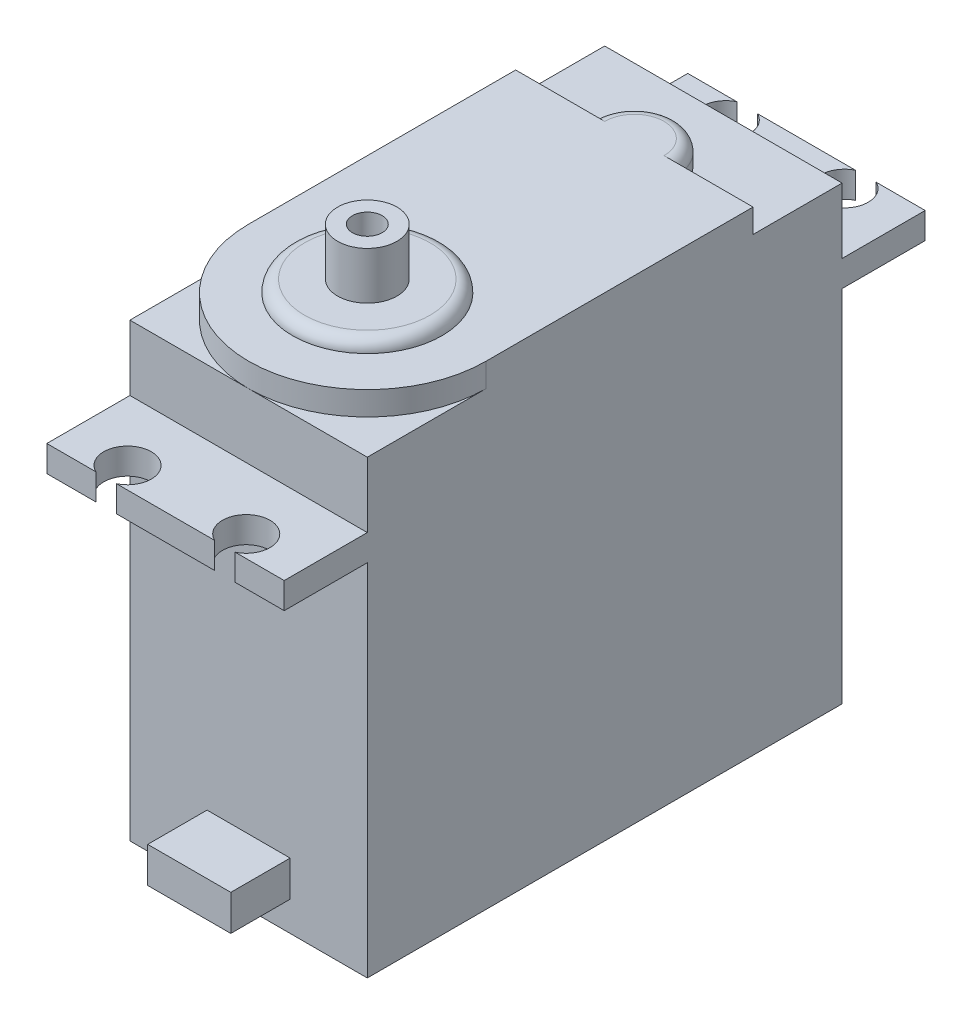
SolidWorks part; units mm, degrees
ref_plane "Front Plane" through (0, 0, 0) normal (0, 0, 1) x (1, 0, 0)
ref_plane "Top Plane" through (0, 0, 0) normal (0, 1, 0) x (1, 0, 0)
ref_plane "Right Plane" through (0, 0, 0) normal (1, 0, 0) x (0, 0, -1)
sketch "Sketch1" plane through (0, 0, 0) normal (0, 1, 0) x (1, 0, 0)
  line L1 (0, 0) -> (20, 0)
  line L2 (0, 0) -> (0, 40)
  line L3 (0, 40) -> (20, 40)
  line L4 (20, 0) -> (20, 40)
  dimension "D1" = 40
  dimension "D2" = 20
extrude "Boss-Extrude1" add sketch "Sketch1" along normal blind 38
sketch "Sketch2" plane through (0, 0, 0) normal (0, 0, 1) x (1, 0, 0)
  line L0 (6.5, 2.5) -> (0, 0) construction
  line L1 (6.5, 2.5) -> (13.5, 2.5)
  line L2 (6.5, 2.5) -> (6.5, 5.5)
  line L3 (6.5, 5.5) -> (13.5, 5.5)
  line L4 (13.5, 2.5) -> (13.5, 5.5)
  line L5 (13.5, 2.5) -> (20, 0) construction
  line L6 (0, 0) -> (20, 0) construction
  dimension "D1" = 7
  dimension "D2" = 3
  dimension "." = 2.5
extrude "Boss-Extrude2" add sketch "Sketch2" along normal blind 5
sketch "Sketch3" plane through (0, 38, 0) normal (0, 1, 0) x (1, 0, 0)
  line L0 (0, 0) -> (20, 0) construction
  line L1 (10, 10) -> (0, 0) construction
  line L2 (10, 10) -> (20, 0) construction
  line L3 (20, 0) -> (20, 40) construction
  circle A0 centre (10, 10) radius 2.5
  dimension "D1" = 10
  dimension "D2" = 5
extrude "Boss-Extrude3" add sketch "Sketch3" along normal blind 7
sketch "Sketch4" plane through (0, 0, 0) normal (0, 0, 1) x (1, 0, 0)
  line L0 (0, 38) -> (0, 0) construction
  line L1 (0, 32.5) -> (20, 32.5)
  line L2 (0, 32.5) -> (0, 30.3)
  line L3 (0, 30.3) -> (20, 30.3)
  line L4 (20, 32.5) -> (20, 30.3)
  line L5 (20, 38) -> (20, 0) construction
  line L6 (0, 38) -> (20, 38) construction
  dimension "D1" = 2.2
  dimension "D2" = 5.5
extrude "Boss-Extrude4" add sketch "Sketch4" along normal blind 7 and the other way blind 47
sketch "Sketch5" plane through (0, 32.5, 0) normal (0, 1, 0) x (1, 0, 0)
  line L0 (15, 45.2) -> (20, 47) construction
  line L1 (5, 45.2) -> (0, 47) construction
  line L2 (5, 45.2) -> (15, 45.2) construction
  line L3 (20, 40) -> (0, 40) construction
  line L4 (15, 45.2) -> (15, -5.2) construction
  line L5 (0, 0) -> (20, 0) construction
  circle A0 centre (15, 45.2) radius 2
  circle A1 centre (5, 45.2) radius 2
  circle A2 centre (15, -5.2) radius 2
  circle A3 centre (5, -5.2) radius 2
  dimension "D1" = 4
  dimension "D2" = 10
  dimension "D3" = 5.2
  dimension "D4" = 5.2
extrude "Cut-Extrude1" cut sketch "Sketch5" against normal blind 7
sketch "Sketch6" plane through (0, 38, 0) normal (0, 1, 0) x (1, 0, 0)
  line L0 (20, 0) -> (20, 40) construction
  line L1 (20, 32.5) -> (13.5, 32.5)
  line L2 (20, 32.5) -> (20, 10)
  line L4 (0, 32.5) -> (0, 10)
  line L5 (6.5, 32.5) -> (0, 32.5)
  line L6 (0, 40) -> (0, 0) construction
  line L7 (20, 40) -> (0, 40) construction
  arc A0 (0, 10) -> (20, 10) centre (10, 10) ccw
  circle A1 centre (10, 10) radius 2.5 construction
  arc A2 (13.5, 32.5) -> (6.5, 32.5) centre (10, 32.5) ccw
  dimension "D1" = 3.5
  dimension "D2" = 7.5
extrude "Boss-Extrude5" add sketch "Sketch6" along normal blind 2
sketch "Sketch7" plane through (0, 40, 0) normal (0, 1, 0) x (1, 0, 0)
  circle A0 centre (10, 10) radius 6.2895
  circle A1 centre (10, 10) radius 2.5 construction
extrude "Boss-Extrude6" add sketch "Sketch7" along normal blind 1
fillet "Fillet1" radius 1 1 edges at (10, 41, -3.7105)
fillet "Fillet2" radius 1 1 edges at (10, 40, -36)
sketch "Sketch8" plane through (0, 45, 0) normal (0, 1, 0) x (1, 0, 0)
  circle A0 centre (10, 10) radius 1.25
  dimension "D1" = 2.5
extrude "Cut-Extrude2" cut sketch "Sketch8" against normal blind 5
sketch "Sketch9" plane through (20, 0, 0) normal (1, 0, 0) x (0, 0, -1)
  line L4 (0, 2.5) -> (0, 5.5)
  line L5 (0, 5.5) -> (-5, 5.5)
  line L6 (-5, 5.5) -> (-5, 2.5)
  line L7 (-5, 2.5) -> (0, 2.5)
  line L8 (0, 2.5) -> (0, 5.5)
  line L9 (0, 5.5) -> (-5, 5.5)
  line L10 (-5, 5.5) -> (-5, 2.5)
  line L11 (-5, 2.5) -> (0, 2.5)
  line L16 (40, 0) -> (40, 30.3)
  line L17 (40, 30.3) -> (47, 30.3)
  line L18 (47, 30.3) -> (47, 32.5)
  line L19 (47, 32.5) -> (40, 32.5)
  line L20 (40, 32.5) -> (40, 38)
  line L21 (40, 38) -> (32.5, 38)
  line L22 (32.5, 38) -> (32.5, 40)
  line L23 (32.5, 40) -> (10, 40)
  line L24 (10, 40) -> (10, 38)
  line L25 (10, 38) -> (0, 38)
  line L26 (0, 38) -> (0, 32.5)
  line L27 (0, 32.5) -> (-7, 32.5)
  line L28 (-7, 32.5) -> (-7, 30.3)
  line L29 (-7, 30.3) -> (0, 30.3)
  line L30 (0, 30.3) -> (0, 0)
  line L31 (0, 0) -> (40, 0)
  line L32 (40, 0) -> (40, 30.3)
  line L33 (40, 30.3) -> (47, 30.3)
  line L34 (47, 30.3) -> (47, 32.5)
  line L35 (47, 32.5) -> (40, 32.5)
  line L36 (40, 32.5) -> (40, 38)
  line L37 (40, 38) -> (32.5, 38)
  line L38 (32.5, 38) -> (32.5, 40)
  line L39 (32.5, 40) -> (10, 40)
  line L40 (10, 40) -> (10, 38)
  line L41 (10, 38) -> (0, 38)
  line L42 (0, 38) -> (0, 32.5)
  line L43 (0, 32.5) -> (-7, 32.5)
  line L44 (-7, 32.5) -> (-7, 30.3)
  line L45 (-7, 30.3) -> (0, 30.3)
  line L46 (0, 30.3) -> (0, 0)
  line L47 (0, 0) -> (40, 0)
  dimension "D1" = 0
  dimension "D2" = 0
